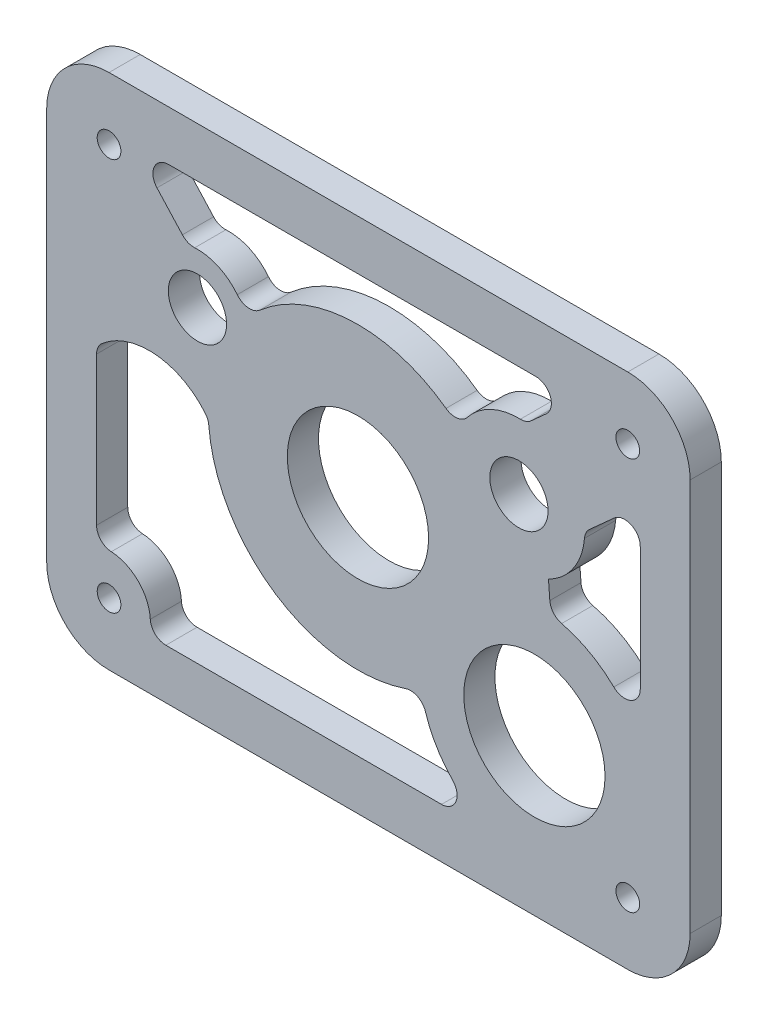
SolidWorks part; units mm, degrees
material "6061-T6 (SS)"
ref_plane "Front Plane" through (0, 0, 0) normal (0, 0, 1) x (1, 0, 0)
ref_plane "Top Plane" through (0, 0, 0) normal (0, 1, 0) x (1, 0, 0)
ref_plane "Right Plane" through (0, 0, 0) normal (1, 0, 0) x (0, 0, -1)
sketch "Sketch1" plane through (0, 0, 0) normal (0, 0, 1) x (1, 0, 0)
  line L1 (-50.7009, 49.5878) -> (54.9631, 49.5878)
  line L2 (-63.4009, 36.8878) -> (-63.4009, -43.1222)
  line L3 (-50.7009, -55.8222) -> (54.9631, -55.8222)
  line L4 (67.6631, 36.8878) -> (67.6631, -43.1222)
  circle A2 centre (0, 0) radius 14.3891
  circle A3 centre (35.9392, -24.0722) radius 14.3891
  circle A4 centre (32.7915, 16.9346) radius 30.48 construction
  circle A6 centre (0, 0) radius 29.21 construction
  circle A7 centre (32.7915, 16.9346) radius 5.9309
  circle A9 centre (0, 0) radius 11.43 construction
  circle A10 centre (35.9392, -24.0722) radius 31.75 construction
  circle A13 centre (32.7915, 16.9346) radius 7.62 construction
  circle A14 centre (-32.6926, 17.1249) radius 30.48 construction
  circle A15 centre (-32.6926, 17.1249) radius 5.9309
  circle A16 centre (-32.6926, 17.1249) radius 7.62 construction
  arc A17 (-50.7009, -55.8222) -> (-63.4009, -43.1222) centre (-50.7009, -43.1222) cw
  arc A18 (54.9631, -55.8222) -> (67.6631, -43.1222) centre (54.9631, -43.1222) ccw
  arc A19 (54.9631, 49.5878) -> (67.6631, 36.8878) centre (54.9631, 36.8878) cw
  arc A20 (-50.7009, 49.5878) -> (-63.4009, 36.8878) centre (-50.7009, 36.8878) ccw
  point P23 (76.1528, -50.8254)
  point P28 (0, 0)
  point P30 (-35.7401, 6.957)
  point P31 (-68.1151, 61.3304)
  point P32 (0, 0)
  point P33 (28.0552, 21.8017)
  point P34 (-33.8168, 13.4974)
  point P35 (34.2781, -26.2588)
  point P36 (65.2062, 41.6132)
  point P37 (0, 0)
  point P38 (25.4738, 64.7229)
  point P39 (45.6728, -39.676)
  point P40 (59.1247, -40.2842)
  point P41 (67.6892, -43.1222)
  point P42 (30.9312, 14.9378)
  point P43 (-32.2573, 11.8534)
  point P44 (33.19, 16.1398)
  point P45 (-32.2361, 17.9695)
  point P46 (32.7915, 16.9346)
  point P47 (-30.9466, 20.1091)
  point P48 (-32.6926, 16.9346)
  dimension "D1" = 60.96
  dimension "D2" = 60.96
  dimension "D3" = 28.7782
  dimension "D4" = 28.7782
  dimension "D6" = 58.42
  dimension "D7" = 11.8618
  dimension "D8" = 11.8618
  dimension "D9" = 22.86
  dimension "D10" = 63.5
  dimension "D11" = 15.24
  dimension "D12" = 15.24
  dimension "D13" = 36.9062
  dimension "D14" = 36.9062
  dimension "D15" = 43.2562
  dimension "D5" = 12.7
  dimension "D16" = 131.064
  dimension "D17" = 105.41
extrude "Boss-Extrude2" add sketch "Sketch1" along normal blind 6.35 contours A13 A6 A4 | A4 | A4 A6 A3 | A13 A6 A4 A9 | A4 A9 A2 | A14 A9 A4 A6 | A16 A6 A14 A9 | A9 A14 A2 | A14 A6 A3 A9 | A14 A9 A3 A4 A2 | A16 A6 A14 | A14 A6 A4 | A6 A14 | A6 region at (2.1311, 47.9058, 0)
sketch "Sketch2" plane through (0, 0, 6.35) normal (0, 0, 1) x (1, 0, 0)
  line L0 (-50.7009, 49.5878) -> (54.9631, 49.5878) construction
  line L1 (-63.4009, 36.8878) -> (-63.4009, -43.1222) construction
  line L2 (2.1311, 49.5878) -> (2.1311, -55.8222) construction
  line L3 (-50.7009, -55.8222) -> (54.9631, -55.8222) construction
  line L4 (-63.4009, -3.1172) -> (67.6631, -3.1172) construction
  line L5 (67.6631, 36.8878) -> (67.6631, -43.1222) construction
  circle A0 centre (-50.7009, 36.8878) radius 2.413
  circle A1 centre (54.9631, 36.8878) radius 2.413
  circle A2 centre (54.9631, -43.1222) radius 2.413
  circle A3 centre (-50.7009, -43.1222) radius 2.413
  dimension "D1" = 4.826
  dimension "D2" = 12.7
  dimension "D3" = 12.7
extrude "Cut-Extrude1" cut sketch "Sketch2" against normal blind 6.35
sketch "Sketch3" plane through (0, 0, 6.35) normal (0, 0, 1) x (1, 0, 0)
  line L0 (0, 0) -> (32.7915, 16.9346)
  line L1 (0, -5.7174) -> (32.7915, 11.2172)
  line L2 (0, 5.7174) -> (32.7915, 22.6521)
  line L3 (32.7915, 16.9346) -> (35.9392, -24.0722)
  line L4 (27.6966, 16.9346) -> (30.2518, -16.354)
  line L5 (37.8865, 16.9346) -> (40.5993, -18.4067)
  line L9 (54.9631, -35.9331) -> (57.5031, -38.4766)
  line L10 (46.1885, 17.0312) -> (57.5031, 27.2137)
  line L11 (-50.7009, 36.8878) -> (-32.6926, 17.1249)
  line L12 (-32.6926, 17.1249) -> (46.1875, 17.1249)
  line L13 (32.7915, 16.9346) -> (54.9631, 36.8878)
  line L14 (-34.6608, 27.2222) -> (-45.7827, 39.4278)
  line L15 (54.9631, 48.8477) -> (30.1298, 26.4992)
  line L31 (35.9392, -24.0722) -> (54.9631, -43.1222)
  line L32 (35.9392, -16.8831) -> (54.9631, -35.9331)
  line L33 (35.9392, -31.2614) -> (54.9631, -50.3114)
  line L35 (57.5031, -43.1222) -> (57.5031, 36.8878)
  line L36 (-50.7009, -45.6622) -> (54.9631, -45.6622)
  line L37 (-53.2409, 36.8878) -> (-53.2409, -43.1222)
  line L38 (54.9631, 39.4278) -> (-50.7009, 39.4278)
  line L39 (57.5031, -43.1222) -> (57.5031, 36.8878)
  line L40 (-50.7009, -45.6622) -> (54.9631, -45.6622)
  line L41 (-53.2409, 36.8878) -> (-53.2409, -43.1222)
  line L42 (54.9631, 39.4278) -> (-50.7009, 39.4278)
  circle A0 centre (35.9392, -24.0722) radius 23.2257
  circle A1 centre (32.7915, 16.9346) radius 13.3973
  circle A2 centre (-32.6926, 17.1249) radius 10.2874
  circle A5 centre (0, 0) radius 30.488
  arc A6 (-53.2409, 0) -> (-29.2611, -3.5854) centre (-42.496, -10.1192) cw
  circle A7 centre (-50.7009, -43.1222) radius 8.4145
  arc A21 (57.5031, 36.8878) -> (54.9631, 39.4278) centre (54.9631, 36.8878) ccw
  arc A22 (54.9631, -45.6622) -> (57.5031, -43.1222) centre (54.9631, -43.1222) ccw
  arc A23 (-53.2409, -43.1222) -> (-50.7009, -45.6622) centre (-50.7009, -43.1222) ccw
  arc A24 (-50.7009, 39.4278) -> (-53.2409, 36.8878) centre (-50.7009, 36.8878) ccw
  arc A25 (57.5031, 36.8878) -> (54.9631, 39.4278) centre (54.9631, 36.8878) ccw
  arc A26 (54.9631, -45.6622) -> (57.5031, -43.1222) centre (54.9631, -43.1222) ccw
  arc A27 (-53.2409, -43.1222) -> (-50.7009, -45.6622) centre (-50.7009, -43.1222) ccw
  arc A28 (-50.7009, 39.4278) -> (-53.2409, 36.8878) centre (-50.7009, 36.8878) ccw
  point P10 (0, 0)
  point P11 (-30.9499, 14.9378)
  point P12 (0, 0)
  point P13 (30.9312, 14.9765)
  point P38 (0, 0)
  point P40 (0, 0)
  dimension "D6" = 29.2611
  dimension "D1" = 5.08
  dimension "D2" = 5.08
  dimension "D3" = 5.08
  dimension "D4" = 5.08
  dimension "D8" = 5.08
  dimension "D9" = 5.08
  dimension "D10" = 8.89
  dimension "D11" = 8.89
  dimension "D7" = 10.16
extrude "Cut-Extrude6" cut sketch "Sketch3" against normal blind 25.4 contours A1 L15 L42 L14 | A1 L5 A0 L32 L9 L39 L10 | A6 L41 A7 L40 A0 region at (-2.3786, 33.4798, 6.35) region at (-25.7398, -27.0485, 6.35) region at (50.8558, 6.4814, 6.35)
fillet "Fillet4" radius 3.175 9 edges at (57.5031, 27.2137, 3.175) (44.4959, 39.4278, 3.175) (46.1885, 17.0312, 3.175) (-45.7827, 39.4278, 3.175) (39.2698, -1.0866, 3.175) (34.2948, 30.2474, 3.175) (-34.6608, 27.2222, 3.175) (-22.8653, 20.1668, 3.175) (57.5031, -15.4449, 3.175)
fillet "Fillet6" radius 3.175 1 edges at (20.5956, 22.4798, 3.175)
fillet "Fillet5" radius 3.175 6 edges at (27.3774, -45.6622, 3.175) (12.9809, -27.5865, 3.175) (-30.4463, -1.5953, 3.175) (-53.2409, 0, 3.175) (-42.6789, -45.6622, 3.175) (-53.2409, -35.1002, 3.175)
